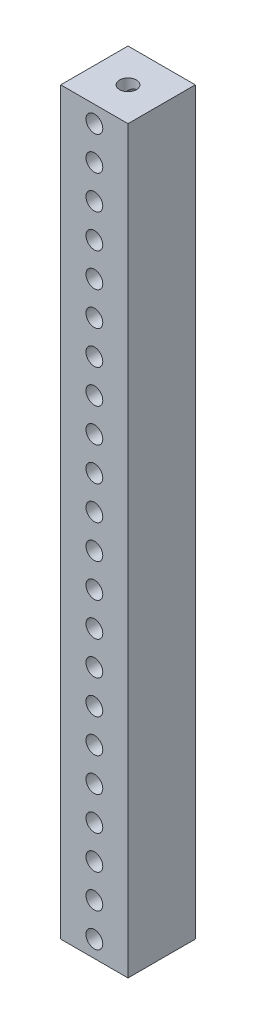
SolidWorks part; units mm, degrees
ref_plane "Front Plane" through (0, 0, 0) normal (0, 0, 1) x (1, 0, 0)
ref_plane "Top Plane" through (0, 0, 0) normal (0, 1, 0) x (1, 0, 0)
ref_plane "Right Plane" through (0, 0, 0) normal (1, 0, 0) x (0, 0, -1)
sketch "Sketch2" plane through (0, 0, 0) normal (0, 1, 0) x (1, 0, 0)
  line L1 (-10, -10) -> (10, -10)
  line L2 (-10, -10) -> (-10, 10)
  line L3 (-10, 10) -> (10, 10)
  line L4 (10, -10) -> (10, 10)
  line L5 (-10, -10) -> (10, 10) construction
  line L6 (-10, 10) -> (10, -10) construction
  circle A0 centre (0, 0) radius 2.5
  point P0 (0, 0)
  dimension "D3" = 5
  dimension "D1" = 20
  dimension "D2" = 20
extrude "Boss-Extrude1" add sketch "Sketch2" along normal blind 220
sketch "Sketch3" plane through (0, 0, 10) normal (0, 0, 1) x (1, 0, 0)
  line L0 (0, -1000) -> (0, 49000) construction
  line L1 (-10, 0) -> (10, 0) construction
  circle A0 centre (0, 5) radius 2.5
  dimension "D1" = 5
  dimension "D2" = 5
extrude "Cut-Extrude1" cut sketch "Sketch3" against normal through all
pattern_linear "LPattern1" count 20 spacing 10 along (0, 1, 0) of "Cut-Extrude1"
sketch "Sketch4" plane through (0, 0, 10) normal (0, 0, 1) x (1, 0, 0)
  line L0 (0, -790) -> (0, 49210) construction
  line L1 (-10, 220) -> (10, 220) construction
  circle A0 centre (0, 215) radius 2.5
  circle A1 centre (0, 205) radius 2.5
  point P5 (0, 220)
  dimension "D1" = 5
  dimension "D2" = 5
  dimension "D4" = 15
  dimension "D3" = 5
extrude "Cut-Extrude2" cut sketch "Sketch4" against normal through all
